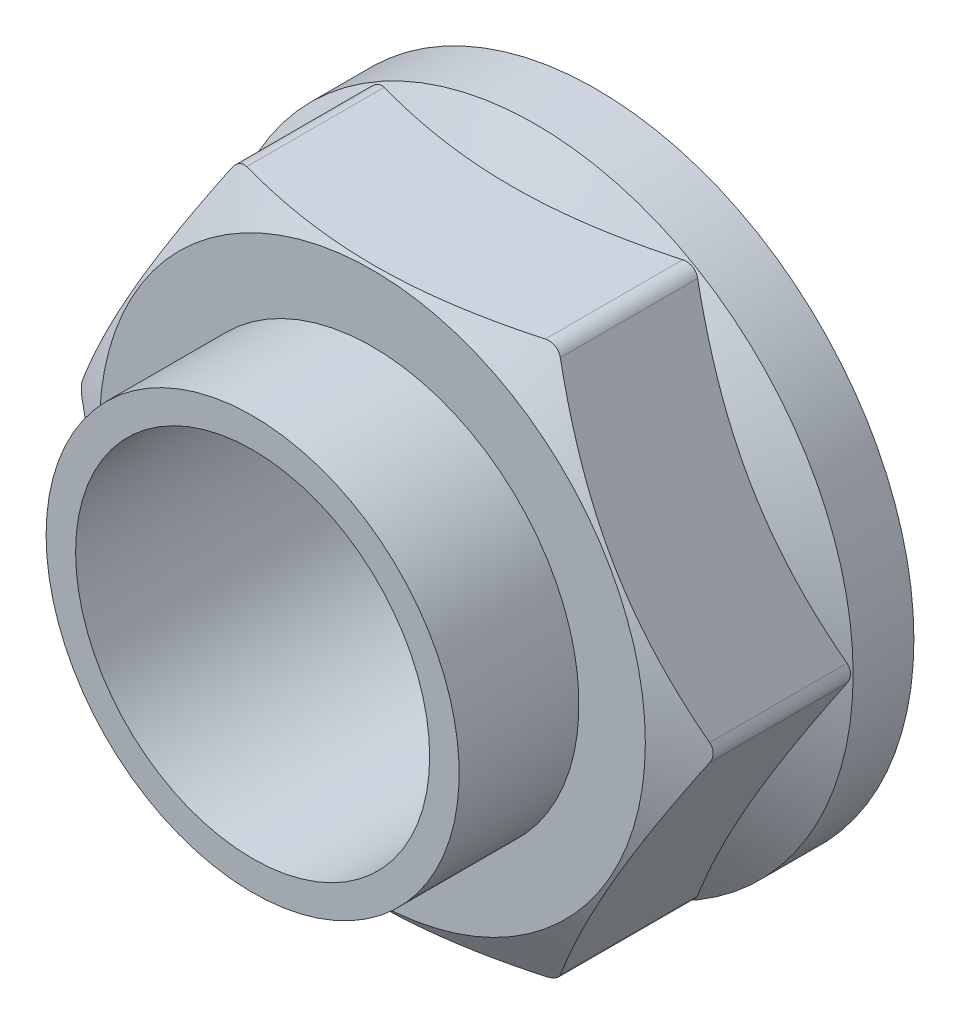
SolidWorks part; units mm, degrees
ref_plane "Front Plane" through (0, 0, 0) normal (0, 0, 1) x (1, 0, 0)
ref_plane "Top Plane" through (0, 0, 0) normal (0, 1, 0) x (1, 0, 0)
ref_plane "Right Plane" through (0, 0, 0) normal (1, 0, 0) x (0, 0, -1)
sketch "Sketch1" plane through (0, 0, 0) normal (1, 0, 0) x (0, 0, -1)
  line L0 (-27.7585, 0) -> (27.7585, 0) construction
  line L1 (0, 10.2) -> (0, 18.3)
  line L2 (0, 18.3) -> (-3.5, 18.3)
  line L3 (-3.5, 18.3) -> (-8.1765, 10.2)
  line L4 (-8.1765, 10.2) -> (0, 10.2)
  dimension "D1" = 20.4
  dimension "D2" = 36.6
  dimension "D3" = 60
  dimension "D4" = 3.5
revolve "Revolve1" add sketch "Sketch1" angle 360 about L0
sketch "Sketch2" plane through (0, 0, 0) normal (0, 0, 1) x (1, 0, 0)
  line L1 (18.0711, 0.5) -> (9.4685, 15.4)
  line L2 (8.6025, 15.9) -> (-8.6025, 15.9)
  line L3 (-9.4685, 15.4) -> (-18.0711, 0.5)
  line L4 (-18.0711, -0.5) -> (-9.4685, -15.4)
  line L5 (-8.6025, -15.9) -> (8.6025, -15.9)
  line L6 (9.4685, -15.4) -> (18.0711, -0.5)
  circle A0 centre (0, 0) radius 15.9 construction
  circle A1 centre (0, 0) radius 10.2
  arc A2 (-18.0711, 0.5) -> (-18.0711, -0.5) centre (-17.205, 0) ccw
  arc A3 (-9.4685, -15.4) -> (-8.6025, -15.9) centre (-8.6025, -14.9) ccw
  arc A4 (8.6025, -15.9) -> (9.4685, -15.4) centre (8.6025, -14.9) ccw
  arc A5 (18.0711, 0.5) -> (18.0711, -0.5) centre (17.205, 0) cw
  arc A6 (9.4685, 15.4) -> (8.6025, 15.9) centre (8.6025, 14.9) ccw
  arc A7 (-8.6025, 15.9) -> (-9.4685, 15.4) centre (-8.6025, 14.9) ccw
  dimension "D2" = 1
  dimension "D1" = 31.8
extrude "Boss-Extrude1" add sketch "Sketch2" along normal blind 12.9
sketch "Sketch3" plane through (0, 0, 0) normal (1, 0, 0) x (0, 0, -1)
  line L0 (-11.4144, 18.3) -> (-21.9799, 0)
  line L2 (-21.9799, 0) -> (-22.5882, 0)
  line L3 (-22.5882, 0) -> (-22.5882, 18.3)
  line L4 (-22.5882, 18.3) -> (-11.4144, 18.3)
  line L5 (0, 0) -> (-28.8725, 0) construction
  line L6 (0, -18.3) -> (0, 18.3) construction
  line L7 (0, 18.3) -> (-3.5, 18.3) construction
  line L8 (-12.9, 15.9) -> (-3.6282, 15.9) construction
  point P11 (-12.8, 15.9)
  dimension "D1" = 12.8
  dimension "D2" = 60
revolve "Cut-Revolve2" cut sketch "Sketch3" angle 360 about L5
sketch "Sketch4" plane through (0, 0, 0) normal (0, 0, 1) x (1, 0, 0)
  circle A0 centre (0, 0) radius 10.2
  circle A1 centre (0, 0) radius 11.9
  dimension "D1" = 1.7
extrude "Boss-Extrude2" add sketch "Sketch4" along normal blind 19.8
